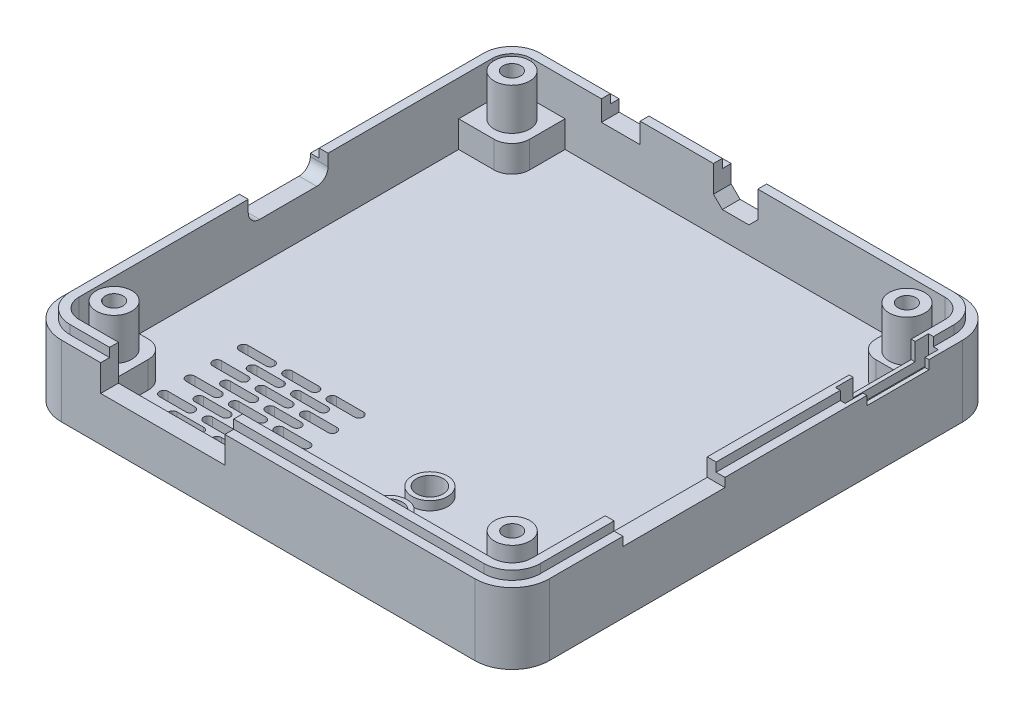
SolidWorks part; units mm, degrees
ref_plane "Front Plane" through (0, 0, 0) normal (0, 0, 1) x (1, 0, 0)
ref_plane "Top Plane" through (0, 0, 0) normal (0, 1, 0) x (1, 0, 0)
ref_plane "Right Plane" through (0, 0, 0) normal (1, 0, 0) x (0, 0, -1)
sketch "Sketch1" plane through (0, 0, 0) normal (0, 1, 0) x (1, 0, 0)
  line L0 (-19.515, 25.5) -> (-19.515, 21.5)
  line L1 (-23.315, 25.5) -> (23.315, 25.5)
  line L2 (-25.515, 23.3) -> (-25.515, -23.3)
  line L3 (-23.315, -25.5) -> (23.315, -25.5)
  line L4 (25.515, 23.3) -> (25.515, -23.3)
  line L5 (-25.515, 25.5) -> (25.515, -25.5) construction
  line L6 (-25.515, -25.5) -> (25.515, 25.5) construction
  line L7 (19.515, 25.5) -> (19.515, 21.5)
  line L8 (-25.515, 19.5) -> (-21.515, 19.5)
  line L9 (-25.515, -19.5) -> (-21.515, -19.5)
  line L10 (-19.515, -21.5) -> (-19.515, -25.5)
  line L11 (21.515, 19.5) -> (25.515, 19.5)
  line L12 (19.515, -21.5) -> (19.515, -25.5)
  line L13 (21.515, -19.5) -> (25.515, -19.5)
  line L14 (-23.315, 26.5) -> (23.315, 26.5)
  line L15 (26.515, 23.3) -> (26.515, -23.3)
  line L16 (-23.315, -26.5) -> (23.315, -26.5)
  line L17 (-26.515, 23.3) -> (-26.515, -23.3)
  line L18 (-23.315, 27.5) -> (23.315, 27.5)
  line L19 (27.515, 23.3) -> (27.515, -23.3)
  line L20 (-23.315, -27.5) -> (23.315, -27.5)
  line L21 (-27.515, 23.3) -> (-27.515, -23.3)
  arc A0 (25.515, -23.3) -> (23.315, -25.5) centre (23.315, -23.3) cw
  arc A1 (-23.315, -25.5) -> (-25.515, -23.3) centre (-23.315, -23.3) cw
  arc A2 (25.515, 23.3) -> (23.315, 25.5) centre (23.315, 23.3) ccw
  arc A3 (-23.315, 25.5) -> (-25.515, 23.3) centre (-23.315, 23.3) ccw
  circle A4 centre (-22.495, 22.49) radius 1
  circle A5 centre (22.425, 22.11) radius 1
  circle A6 centre (-22.455, -22.41) radius 1
  circle A7 centre (22.445, -22.42) radius 1
  arc A8 (21.515, -19.5) -> (19.515, -21.5) centre (21.515, -21.5) ccw
  arc A9 (-19.515, -21.5) -> (-21.515, -19.5) centre (-21.515, -21.5) ccw
  arc A10 (21.515, 19.5) -> (19.515, 21.5) centre (21.515, 21.5) cw
  arc A11 (-19.515, 21.5) -> (-21.515, 19.5) centre (-21.515, 21.5) cw
  arc A12 (26.515, 23.3) -> (23.315, 26.5) centre (23.315, 23.3) ccw
  arc A13 (26.515, -23.3) -> (23.315, -26.5) centre (23.315, -23.3) cw
  arc A14 (-23.315, -26.5) -> (-26.515, -23.3) centre (-23.315, -23.3) cw
  arc A15 (-23.315, 26.5) -> (-26.515, 23.3) centre (-23.315, 23.3) ccw
  arc A16 (27.515, 23.3) -> (23.315, 27.5) centre (23.315, 23.3) ccw
  arc A17 (27.515, -23.3) -> (23.315, -27.5) centre (23.315, -23.3) cw
  arc A18 (-23.315, -27.5) -> (-27.515, -23.3) centre (-23.315, -23.3) cw
  arc A19 (-23.315, 27.5) -> (-27.515, 23.3) centre (-23.315, 23.3) ccw
  point P0 (0, 0)
  point P40 (19.515, -19.5)
  dimension "D3" = 2.2
  dimension "D4" = 2
  dimension "D5" = 3.01
  dimension "D6" = 3.02
  dimension "D7" = 2
  dimension "D8" = 3.39
  dimension "D9" = 3.09
  dimension "D10" = 2
  dimension "D11" = 3.09
  dimension "D12" = 3.06
  dimension "D13" = 2
  dimension "D14" = 3.08
  dimension "D15" = 3.07
  dimension "D21" = 2
  dimension "D1" = 51.03
  dimension "D2" = 51
  dimension "D16" = 6
  dimension "D17" = 6
  dimension "D18" = 6
  dimension "D19" = 6
  dimension "D20" = 6
  dimension "D24" = 53.03
  dimension "D25" = 55.03
  dimension "D22" = 1
  dimension "D23" = 1
extrude "Boss-Extrude1" add sketch "Sketch1" along normal blind 8 contours L18 A19 L21 A18 L20 A17 L19 A16 A15 L14 A12 L15 A13 L16 A14 L17 region at (0, 0, -26.722)
extrude "Boss-Extrude2" add sketch "Sketch1<3>" along normal blind 9 contours L14 A15 L17 A14 L16 A13 L15 A12 A3 L1 A2 L4 A0 L3 A1 L2 region at (0, 0, -25.7503)
sketch "Sketch1<3>" plane through (0, 0, 0) normal (0, 1, 0) x (1, 0, 0) same geometry as "Sketch1"
extrude "Boss-Extrude3" add sketch "Sketch1<4>" along normal blind 2 contours L0 A11 L8 L2 L9 A9 L10 L3 L12 A8 L13 L4 L11 A10 L7 L1 region at (0, 0, 0)
sketch "Sketch1<4>" plane through (0, 0, 0) normal (0, 1, 0) x (1, 0, 0) same geometry as "Sketch1"
extrude "Boss-Extrude4" add sketch "Sketch1<5>" along normal blind 5 contours A11 L0 L1 A3 L2 L8 A4 | L10 A9 L9 L2 A1 L3 A6 | L13 A8 L12 L3 A0 L4 A7 | A10 L11 L4 A2 L1 L7 A5 | A4 | A5 | A7 | A6 region at (-19.5999, 0, -23.5) region at (21.415, 0, -25.4151) region at (-23.515, 0, 19.5849) region at (25.4301, 0, 21.4)
sketch "Sketch1<5>" plane through (0, 0, 0) normal (0, 1, 0) x (1, 0, 0) same geometry as "Sketch1"
sketch "Sketch3" plane through (0, 0, -26.5) normal (0, 0, -1) x (-1, 0, 0)
  line L0 (23.315, 9) -> (-23.315, 9) construction
  line L1 (1.785, 5) -> (-1.215, 5)
  line L2 (2.785, 6) -> (2.785, 9)
  line L3 (2.785, 9) -> (-2.215, 9)
  line L4 (-2.215, 6) -> (-2.215, 9)
  line L5 (2.785, 5) -> (-2.215, 9) construction
  line L6 (2.785, 9) -> (-2.215, 5) construction
  line L7 (0, 0) -> (0, 15.6859) construction
  line L8 (27.515, 8) -> (27.515, 0) construction
  line L9 (-27.515, 8) -> (-27.515, 0) construction
  line L10 (-1.215, 5) -> (-2.215, 6)
  line L11 (2.785, 6) -> (1.785, 5)
  line L13 (11.055, 9) -> (15.415, 9)
  line L14 (11.055, 9) -> (11.055, 6.7)
  line L15 (11.055, 6.7) -> (15.415, 6.7)
  line L16 (15.415, 9) -> (15.415, 6.7)
  point P0 (0.285, 7)
  dimension "D1" = 4
  dimension "D2" = 5
  dimension "D3" = 24.73
  dimension "D4" = 25.3
  dimension "D5" = 2.3
  dimension "D6" = 4.36
  dimension "D9" = 12.1
extrude "Cut-Extrude1" cut sketch "Sketch3" against normal mid plane 2
sketch "Sketch4" plane through (0, 5, 0) normal (0, 1, 0) x (1, 0, 0)
  line L0 (-25.515, -19.5) -> (-25.515, -23.3) construction
  line L1 (-19.515, -25.5) -> (19.515, -25.5) construction
  line L2 (25.515, 19.5) -> (25.515, -19.5) construction
  line L3 (25.515, 23.3) -> (25.515, 19.5) construction
  line L4 (19.515, 25.5) -> (23.315, 25.5) construction
  line L5 (-23.315, 25.5) -> (-15.415, 25.5) construction
  line L6 (-25.515, 23.3) -> (-25.515, -23.3) construction
  circle A0 centre (-22.495, 22.49) radius 1
  circle A1 centre (-22.495, 22.49) radius 2
  circle A2 centre (22.425, 22.11) radius 1
  circle A3 centre (22.425, 22.11) radius 2
  circle A4 centre (22.445, -22.42) radius 1
  circle A5 centre (22.445, -22.42) radius 2
  circle A6 centre (-22.455, -22.41) radius 1
  circle A7 centre (-22.455, -22.41) radius 2
  dimension "D1" = 2
  dimension "D2" = 4
  dimension "D3" = 2
  dimension "D4" = 4
  dimension "D5" = 2
  dimension "D6" = 4
  dimension "D7" = 2
  dimension "D8" = 4
  dimension "D9" = 3.06
  dimension "D10" = 3.09
  dimension "D11" = 3.07
  dimension "D12" = 3.08
  dimension "D13" = 3.09
  dimension "D14" = 3.39
  dimension "D15" = 3.01
  dimension "D16" = 3.02
extrude "Boss-Extrude5" add sketch "Sketch4" along normal blind 4.7
sketch "Sketch5" plane through (0, 9, 0) normal (0, 1, 0) x (1, 0, 0)
  line L0 (21.515, 19.5) -> (25.515, 19.5) construction
  line L1 (25.965, 21) -> (27.065, 21)
  line L2 (25.965, 21) -> (25.965, 10.5)
  line L3 (25.965, 10.5) -> (27.065, 10.5)
  line L4 (27.065, 21) -> (27.065, 10.5)
  line L5 (25.515, 23.3) -> (25.515, -23.3) construction
  line L6 (27.515, 23.3) -> (27.515, -23.3) construction
  dimension "D1" = 10.5
  dimension "D2" = 1.5
  dimension "D3" = 1.1
  dimension "D4" = 0.45
  dimension "D5" = 0.45
extrude "Cut-Extrude2" cut sketch "Sketch5" against normal blind 3
sketch "Sketch6" plane through (27.515, 0, 0) normal (1, 0, 0) x (0, 0, -1)
  line L0 (10.5, 9) -> (-23.3, 9) construction
  line L1 (-15, 9) -> (-3.5, 9)
  line L2 (-15, 9) -> (-15, 7)
  line L3 (-15, 7) -> (-3.5, 7)
  line L4 (-3.5, 9) -> (-3.5, 7)
  line L5 (-27.5, 8) -> (-27.5, 0) construction
  line L6 (27.5, 8) -> (27.5, 0) construction
  line L7 (12.5, 9) -> (19.5, 9)
  line L8 (12.5, 9) -> (12.5, 7)
  line L9 (12.5, 7) -> (19.5, 7)
  line L10 (19.5, 9) -> (19.5, 7)
  dimension "D1" = 12.5
  dimension "D2" = 2
  dimension "D3" = 11.5
  dimension "D4" = 2
  dimension "D5" = 7
  dimension "D6" = 8
extrude "Cut-Extrude3" cut sketch "Sketch6" against normal blind 3
sketch "Sketch7" plane through (0, 0, 27.5) normal (0, 0, 1) x (1, 0, 0)
  line L0 (-23.315, 9) -> (23.315, 9) construction
  line L1 (-18.875, 9) -> (-4.875, 9)
  line L2 (-18.875, 9) -> (-18.875, 5)
  line L3 (-18.875, 5) -> (-4.875, 5)
  line L4 (-4.875, 9) -> (-4.875, 5)
  line L5 (-27.515, 8) -> (-27.515, 0) construction
  dimension "D1" = 8.64
  dimension "D2" = 4
  dimension "D3" = 14
extrude "Cut-Extrude4" cut sketch "Sketch7" against normal blind 2
sketch "Sketch8" plane through (-27.515, 0, 0) normal (-1, 0, 0) x (0, 0, 1)
  line L0 (-23.3, 9) -> (23.3, 9) construction
  line L1 (-4.775, 9) -> (4.225, 9)
  line L2 (-4.775, 9) -> (-4.775, 7.68)
  line L3 (-3.495, 6.4) -> (2.945, 6.4)
  line L4 (4.225, 9) -> (4.225, 7.68)
  line L7 (27.5, 8) -> (27.5, 0) construction
  line L8 (-27.5, 8) -> (-27.5, 0) construction
  arc A0 (4.225, 7.68) -> (2.945, 6.4) centre (2.945, 7.68) cw
  arc A1 (-3.495, 6.4) -> (-4.775, 7.68) centre (-3.495, 7.68) cw
  point P8 (4.225, 6.4)
  point P11 (-4.775, 6.4)
  dimension "D2" = 1.28
  dimension "D1" = 9
  dimension "D3" = 2.6
  dimension "D4" = 23.275
  dimension "D5" = 22.725
extrude "Cut-Extrude5" cut sketch "Sketch8" against normal blind 2
sketch "Sketch10" plane through (0, 2, 0) normal (0, 1, 0) x (1, 0, 0)
  line L0 (-19.515, -25.5) -> (19.515, -25.5) construction
  line L1 (25.515, -15) -> (25.515, -23.3) construction
  line L2 (25.515, -15) -> (25.515, -3.5) construction
  circle A0 centre (6.745, -16) radius 1.5
  circle A1 centre (6.745, -20.6) radius 1.5
  circle A2 centre (6.745, -16) radius 2
  circle A3 centre (6.745, -20.6) radius 2
  dimension "D1" = 4.6
  dimension "D2" = 3
  dimension "D3" = 3
  dimension "D4" = 4
  dimension "D5" = 4
  dimension "D6" = 4.9
  dimension "D7" = 18.77
  dimension "D8" = 18.77
extrude "Cut-Extrude6" cut sketch "Sketch10" against normal blind 2 contours A0 | A1
sketch "Sketch11" plane through (0, 0, 0) normal (0, -1, 0) x (1, 0, 0)
  line L0 (-23.315, 27.5) -> (23.315, 27.5) construction
  line L9 (-13.265, 18.5) -> (-10.265, 18.5)
  line L12 (-27.515, -23.3) -> (-27.515, 23.3) construction
  line L13 (-8.265, 18.5) -> (-5.265, 18.5)
  line L16 (-8.265, 17.5) -> (-5.265, 17.5)
  line L20 (-13.265, 17.5) -> (-10.265, 17.5)
  line L22 (-13.265, 18.5) -> (-10.265, 17.5) construction
  line L23 (-13.265, 17.5) -> (-10.265, 18.5) construction
  line L24 (-8.265, 18.5) -> (-5.265, 17.5) construction
  line L25 (-8.265, 17.5) -> (-5.265, 18.5) construction
  line L26 (-18.265, 18.5) -> (-15.265, 18.5)
  line L27 (-18.265, 17.5) -> (-15.265, 17.5)
  line L28 (-18.265, 18.5) -> (-15.265, 17.5) construction
  line L29 (-18.265, 17.5) -> (-15.265, 18.5) construction
  line L32 (-7.765, 19) -> (-10.765, 19)
  line L33 (-21.1636, 18) -> (-2.9441, 18) construction
  line L34 (-11.765, 25.7185) -> (-11.765, 7.8135) construction
  line L37 (-12.765, 19) -> (-15.765, 19)
  line L40 (-19.287, 19.5) -> (-4.3701, 19.5) construction
  line L43 (-12.765, 20) -> (-15.765, 20)
  line L45 (-12.765, 19) -> (-15.765, 20) construction
  line L46 (-12.765, 20) -> (-15.765, 19) construction
  line L47 (-7.765, 20) -> (-10.765, 20)
  line L48 (-7.765, 19) -> (-10.765, 20) construction
  line L49 (-7.765, 20) -> (-10.765, 19) construction
  line L50 (-18.265, 21.5) -> (-15.265, 20.5) construction
  line L51 (-18.265, 20.5) -> (-15.265, 21.5) construction
  line L52 (-8.265, 21.5) -> (-5.265, 20.5) construction
  line L53 (-8.265, 20.5) -> (-5.265, 21.5) construction
  line L54 (-13.265, 21.5) -> (-10.265, 20.5) construction
  line L55 (-13.265, 20.5) -> (-10.265, 21.5) construction
  line L56 (-18.265, 21.5) -> (-15.265, 21.5)
  line L57 (-18.265, 20.5) -> (-15.265, 20.5)
  line L58 (-13.265, 21.5) -> (-10.265, 21.5)
  line L59 (-8.265, 21.5) -> (-5.265, 21.5)
  line L60 (-8.265, 20.5) -> (-5.265, 20.5)
  line L61 (-13.265, 20.5) -> (-10.265, 20.5)
  line L62 (-7.765, 16) -> (-10.765, 17) construction
  line L63 (-7.765, 17) -> (-10.765, 16) construction
  line L64 (-12.765, 16) -> (-15.765, 17) construction
  line L65 (-12.765, 17) -> (-15.765, 16) construction
  line L66 (-7.765, 16) -> (-10.765, 16)
  line L67 (-12.765, 16) -> (-15.765, 16)
  line L68 (-12.765, 17) -> (-15.765, 17)
  line L69 (-7.765, 17) -> (-10.765, 17)
  line L70 (-20.5681, 21) -> (-2.9441, 21) construction
  line L72 (-19.4706, 16.5) -> (-4.9737, 16.5) construction
  line L74 (-7.765, 22) -> (-10.765, 23) construction
  line L75 (-7.765, 23) -> (-10.765, 22) construction
  line L76 (-12.765, 22) -> (-15.765, 23) construction
  line L77 (-12.765, 23) -> (-15.765, 22) construction
  line L78 (-7.765, 22) -> (-10.765, 22)
  line L79 (-12.765, 22) -> (-15.765, 22)
  line L80 (-12.765, 23) -> (-15.765, 23)
  line L81 (-7.765, 23) -> (-10.765, 23)
  line L82 (-19.287, 22.5) -> (-3.1107, 22.5) construction
  line L84 (-13.265, 24.5) -> (-10.265, 23.5) construction
  line L85 (-13.265, 23.5) -> (-10.265, 24.5) construction
  line L86 (-8.265, 24.5) -> (-5.265, 23.5) construction
  line L87 (-8.265, 23.5) -> (-5.265, 24.5) construction
  line L88 (-18.265, 24.5) -> (-15.265, 23.5) construction
  line L89 (-18.265, 23.5) -> (-15.265, 24.5) construction
  line L90 (-13.265, 24.5) -> (-10.265, 24.5)
  line L91 (-8.265, 24.5) -> (-5.265, 24.5)
  line L92 (-8.265, 23.5) -> (-5.265, 23.5)
  line L93 (-13.265, 23.5) -> (-10.265, 23.5)
  line L94 (-18.265, 24.5) -> (-15.265, 24.5)
  line L95 (-18.265, 23.5) -> (-15.265, 23.5)
  line L96 (-18.265, 15.5) -> (-15.265, 14.5) construction
  line L97 (-18.265, 14.5) -> (-15.265, 15.5) construction
  line L98 (-8.265, 15.5) -> (-5.265, 14.5) construction
  line L99 (-8.265, 14.5) -> (-5.265, 15.5) construction
  line L100 (-13.265, 15.5) -> (-10.265, 14.5) construction
  line L101 (-13.265, 14.5) -> (-10.265, 15.5) construction
  line L102 (-18.265, 15.5) -> (-15.265, 15.5)
  line L103 (-18.265, 14.5) -> (-15.265, 14.5)
  line L104 (-13.265, 15.5) -> (-10.265, 15.5)
  line L105 (-8.265, 15.5) -> (-5.265, 15.5)
  line L106 (-8.265, 14.5) -> (-5.265, 14.5)
  line L107 (-13.265, 14.5) -> (-10.265, 14.5)
  line L108 (-20.3609, 15) -> (-2.9441, 15) construction
  line L109 (-12.765, 13) -> (-15.765, 14) construction
  line L110 (-12.765, 14) -> (-15.765, 13) construction
  line L111 (-7.765, 13) -> (-10.765, 14) construction
  line L112 (-7.765, 14) -> (-10.765, 13) construction
  line L113 (-7.765, 13) -> (-10.765, 13)
  line L114 (-12.765, 13) -> (-15.765, 13)
  line L115 (-12.765, 14) -> (-15.765, 14)
  line L116 (-7.765, 14) -> (-10.765, 14)
  line L117 (-18.109, 13.5) -> (-4.7942, 13.5) construction
  line L118 (-13.265, 12.5) -> (-10.265, 11.5) construction
  line L119 (-13.265, 11.5) -> (-10.265, 12.5) construction
  line L120 (-8.265, 12.5) -> (-5.265, 11.5) construction
  line L121 (-8.265, 11.5) -> (-5.265, 12.5) construction
  line L122 (-18.265, 12.5) -> (-15.265, 11.5) construction
  line L123 (-18.265, 11.5) -> (-15.265, 12.5) construction
  line L124 (-13.265, 12.5) -> (-10.265, 12.5)
  line L125 (-8.265, 12.5) -> (-5.265, 12.5)
  line L126 (-8.265, 11.5) -> (-5.265, 11.5)
  line L127 (-13.265, 11.5) -> (-10.265, 11.5)
  line L128 (-18.265, 12.5) -> (-15.265, 12.5)
  line L129 (-18.265, 11.5) -> (-15.265, 11.5)
  line L130 (-20.3609, 12) -> (-3.3294, 12) construction
  arc A48 (-13.265, 18.5) -> (-13.265, 17.5) centre (-13.265, 18) ccw
  arc A49 (-10.265, 18.5) -> (-10.265, 17.5) centre (-10.265, 18) cw
  arc A50 (-8.265, 18.5) -> (-8.265, 17.5) centre (-8.265, 18) ccw
  arc A51 (-5.265, 18.5) -> (-5.265, 17.5) centre (-5.265, 18) cw
  arc A52 (-18.265, 18.5) -> (-18.265, 17.5) centre (-18.265, 18) ccw
  arc A53 (-15.265, 18.5) -> (-15.265, 17.5) centre (-15.265, 18) cw
  arc A58 (-15.765, 20) -> (-15.765, 19) centre (-15.765, 19.5) ccw
  arc A59 (-12.765, 20) -> (-12.765, 19) centre (-12.765, 19.5) cw
  arc A60 (-10.765, 20) -> (-10.765, 19) centre (-10.765, 19.5) ccw
  arc A61 (-7.765, 20) -> (-7.765, 19) centre (-7.765, 19.5) cw
  arc A62 (-15.265, 20.5) -> (-15.265, 21.5) centre (-15.265, 21) ccw
  arc A63 (-18.265, 20.5) -> (-18.265, 21.5) centre (-18.265, 21) cw
  arc A64 (-5.265, 20.5) -> (-5.265, 21.5) centre (-5.265, 21) ccw
  arc A65 (-8.265, 20.5) -> (-8.265, 21.5) centre (-8.265, 21) cw
  arc A66 (-10.265, 20.5) -> (-10.265, 21.5) centre (-10.265, 21) ccw
  arc A67 (-13.265, 20.5) -> (-13.265, 21.5) centre (-13.265, 21) cw
  arc A68 (-7.765, 16) -> (-7.765, 17) centre (-7.765, 16.5) ccw
  arc A69 (-10.765, 16) -> (-10.765, 17) centre (-10.765, 16.5) cw
  arc A70 (-12.765, 16) -> (-12.765, 17) centre (-12.765, 16.5) ccw
  arc A71 (-15.765, 16) -> (-15.765, 17) centre (-15.765, 16.5) cw
  arc A72 (-7.765, 22) -> (-7.765, 23) centre (-7.765, 22.5) ccw
  arc A73 (-10.765, 22) -> (-10.765, 23) centre (-10.765, 22.5) cw
  arc A74 (-12.765, 22) -> (-12.765, 23) centre (-12.765, 22.5) ccw
  arc A75 (-15.765, 22) -> (-15.765, 23) centre (-15.765, 22.5) cw
  arc A76 (-13.265, 24.5) -> (-13.265, 23.5) centre (-13.265, 24) ccw
  arc A77 (-10.265, 24.5) -> (-10.265, 23.5) centre (-10.265, 24) cw
  arc A78 (-8.265, 24.5) -> (-8.265, 23.5) centre (-8.265, 24) ccw
  arc A79 (-5.265, 24.5) -> (-5.265, 23.5) centre (-5.265, 24) cw
  arc A80 (-18.265, 24.5) -> (-18.265, 23.5) centre (-18.265, 24) ccw
  arc A81 (-15.265, 24.5) -> (-15.265, 23.5) centre (-15.265, 24) cw
  arc A82 (-15.265, 14.5) -> (-15.265, 15.5) centre (-15.265, 15) ccw
  arc A83 (-18.265, 14.5) -> (-18.265, 15.5) centre (-18.265, 15) cw
  arc A84 (-5.265, 14.5) -> (-5.265, 15.5) centre (-5.265, 15) ccw
  arc A85 (-8.265, 14.5) -> (-8.265, 15.5) centre (-8.265, 15) cw
  arc A86 (-10.265, 14.5) -> (-10.265, 15.5) centre (-10.265, 15) ccw
  arc A87 (-13.265, 14.5) -> (-13.265, 15.5) centre (-13.265, 15) cw
  arc A88 (-15.765, 14) -> (-15.765, 13) centre (-15.765, 13.5) ccw
  arc A89 (-12.765, 14) -> (-12.765, 13) centre (-12.765, 13.5) cw
  arc A90 (-10.765, 14) -> (-10.765, 13) centre (-10.765, 13.5) ccw
  arc A91 (-7.765, 14) -> (-7.765, 13) centre (-7.765, 13.5) cw
  arc A92 (-13.265, 12.5) -> (-13.265, 11.5) centre (-13.265, 12) ccw
  arc A93 (-10.265, 12.5) -> (-10.265, 11.5) centre (-10.265, 12) cw
  arc A94 (-8.265, 12.5) -> (-8.265, 11.5) centre (-8.265, 12) ccw
  arc A95 (-5.265, 12.5) -> (-5.265, 11.5) centre (-5.265, 12) cw
  arc A96 (-18.265, 12.5) -> (-18.265, 11.5) centre (-18.265, 12) ccw
  arc A97 (-15.265, 12.5) -> (-15.265, 11.5) centre (-15.265, 12) cw
  point P0 (-11.765, 18)
  point P12 (-6.765, 18)
  point P19 (-16.765, 18)
  point P29 (-14.265, 19.5)
  point P38 (-9.265, 19.5)
  point P63 (-16.765, 21)
  point P64 (-6.765, 21)
  point P65 (-11.765, 21)
  point P78 (-9.265, 16.5)
  point P79 (-14.265, 16.5)
  point P96 (-9.265, 22.5)
  point P97 (-14.265, 22.5)
  point P118 (-11.765, 24)
  point P119 (-6.765, 24)
  point P120 (-16.765, 24)
  point P139 (-16.765, 15)
  point P140 (-6.765, 15)
  point P141 (-11.765, 15)
  point P156 (-14.265, 13.5)
  point P157 (-9.265, 13.5)
  point P178 (-11.765, 12)
  point P179 (-6.765, 12)
  point P180 (-16.765, 12)
  dimension "D2" = 1
  dimension "D3" = 9.5
  dimension "D11" = 0.5
  dimension "D12" = 11.75
  dimension "D10" = 1
  dimension "D13" = 2
  dimension "D15" = 1
  dimension "D9" = 1
  dimension "D14" = 3
  dimension "D1" = 3
  dimension "D4" = 15.75
  dimension "D5" = 2
  dimension "D6" = 2
  dimension "D7" = 2
  dimension "D8" = 2
extrude "Cut-Extrude8" cut sketch "Sketch11" against normal blind 2
extrude "Boss-Extrude6" add sketch "Sketch10<3>" along normal blind 1
sketch "Sketch10<3>" plane through (0, 2, 0) normal (0, 1, 0) x (1, 0, 0) same geometry as "Sketch10"
